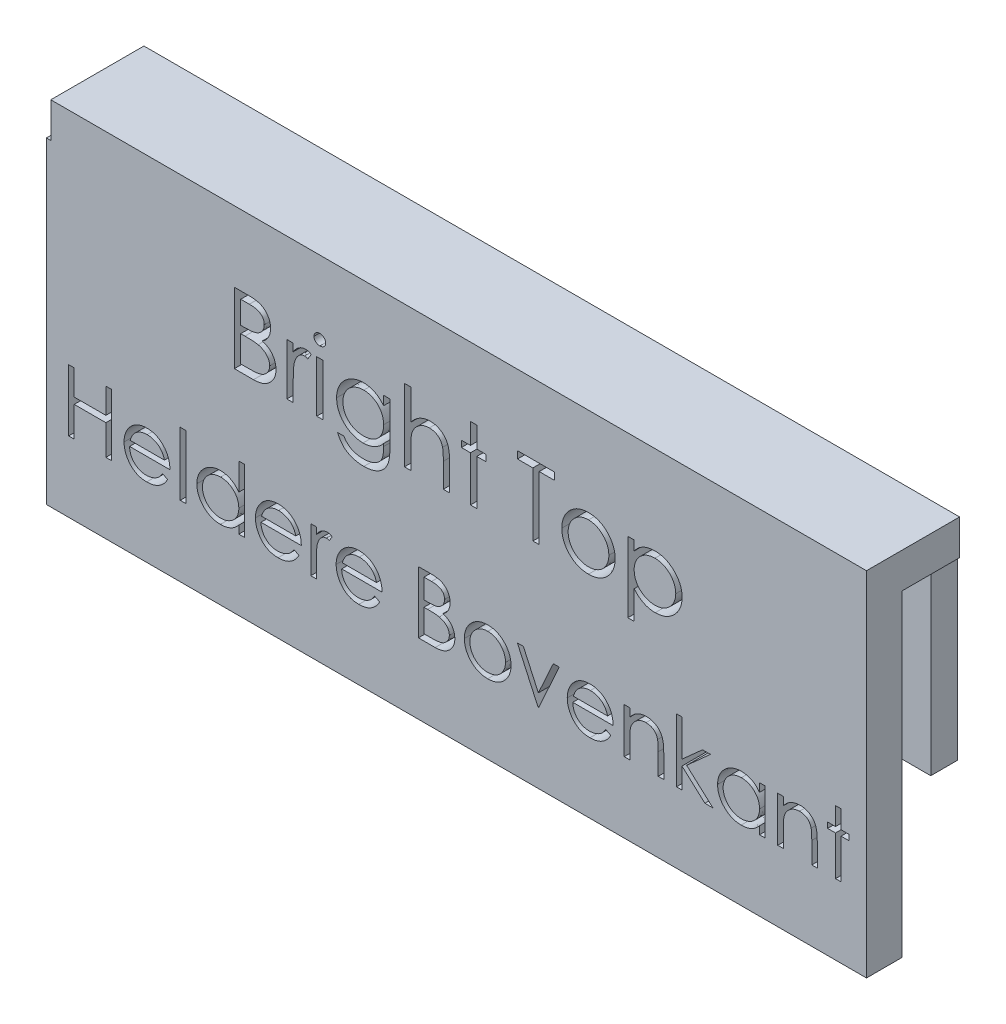
SolidWorks part; units mm, degrees
ref_plane "Front Plane" through (0, 0, 0) normal (0, 0, 1) x (1, 0, 0)
ref_plane "Top Plane" through (0, 0, 0) normal (0, 1, 0) x (1, 0, 0)
ref_plane "Right Plane" through (0, 0, 0) normal (1, 0, 0) x (0, 0, -1)
sketch "Sketch1" plane through (0, 0, 0) normal (0, 0, 1) x (1, 0, 0)
  line L0 (61.5, 25) -> (3, 25) construction
  line L1 (9, 25) -> (55.5, 25)
  line L2 (9, 25) -> (9, 7)
  line L3 (9, 7) -> (55.5, 7)
  line L4 (55.5, 25) -> (55.5, 7)
  line L5 (55.5, 15) -> (55.5, 25) construction
  line L6 (9, 15) -> (9, 25) construction
  line L7 (2, 2) -> (62.5, 2) construction
  dimension "D1" = 5
extrude "Boss-Extrude1" add sketch "Sketch1" along normal blind 2
sketch "Sketch3" plane through (0, 15, 0) normal (0, 1, 0) x (1, 0, 0)
  line L0 (9.2511, 3.2803) -> (9.2511, 1.7537)
  line L5 (9.2511, 1.7537) -> (55.39, 1.7537)
  line L6 (55.39, 3.2803) -> (55.39, 1.7537)
  line L7 (9.2511, 3.2803) -> (55.39, 3.2803)
extrude "Boss-Extrude2" add sketch "Sketch3" along normal up to surface (10 mm away) separate body
sketch "Sketch4" plane through (0, 25, 0) normal (0, 1, 0) x (1, 0, 0)
  line L1 (9.2511, 3.2803) -> (55.5, 3.2803)
  line L2 (9.2511, 3.2803) -> (9.2511, -2)
  line L3 (9.2511, -2) -> (55.5, -2)
  line L4 (55.5, 3.2803) -> (55.5, -2)
extrude "Boss-Extrude3" add sketch "Sketch4" along normal blind 2
sketch "Sketch5" plane through (0, 0, 2) normal (0, 0, 1) x (1, 0, 0)
  line L0 (9, 19) -> (55.5, 19) construction
  line L1 (9, 25) -> (9, 7) construction
  line L2 (55.5, 7) -> (55.5, 27) construction
  line L3 (9.2511, 27) -> (55.5, 27) construction
  line L4 (9, 11) -> (55.5, 11) construction
  line L5 (19.6603, 23) -> (20.4407, 23)
  line L6 (20.742, 19) -> (19.6603, 19)
  line L7 (19.6603, 19) -> (19.6603, 23)
  line L8 (20.0192, 22.5897) -> (20.0192, 21.3077)
  line L9 (20.0192, 21.3077) -> (20.2604, 21.3077)
  line L10 (20.5064, 22.5897) -> (20.0192, 22.5897)
  line L11 (20.0192, 20.8974) -> (20.0192, 19.4103)
  line L12 (20.0192, 19.4103) -> (20.5304, 19.4103)
  line L13 (20.2572, 20.8974) -> (20.0192, 20.8974)
  line L14 (22.6346, 21.9231) -> (22.9936, 21.9231)
  line L15 (22.9936, 21.9231) -> (22.9936, 21.4928)
  line L16 (24.0192, 21.8742) -> (23.8221, 21.5633)
  line L17 (22.9936, 19.9824) -> (22.9936, 19)
  line L18 (22.9936, 19) -> (22.6346, 19)
  line L19 (22.6346, 19) -> (22.6346, 21.9231)
  line L20 (24.3269, 21.9231) -> (24.6859, 21.9231)
  line L21 (24.6859, 21.9231) -> (24.6859, 19)
  line L22 (24.6859, 19) -> (24.3269, 19)
  line L23 (24.3269, 19) -> (24.3269, 21.9231)
  line L24 (28.1218, 21.9231) -> (28.4808, 21.9231)
  line L25 (28.4808, 21.9231) -> (28.4808, 19.6034)
  line L26 (25.5064, 18.7949) -> (25.8654, 18.7949)
  line L27 (28.1218, 19.4087) -> (28.1218, 19.5601)
  line L28 (28.1218, 21.4119) -> (28.1218, 21.9231)
  line L29 (29.3013, 23.1026) -> (29.6603, 23.1026)
  line L30 (29.6603, 23.1026) -> (29.6603, 21.371)
  line L31 (31.8654, 20.4928) -> (31.8654, 19)
  line L32 (31.8654, 19) -> (31.5064, 19)
  line L33 (31.5064, 19) -> (31.5064, 20.375)
  line L34 (29.6603, 20.0569) -> (29.6603, 19)
  line L35 (29.6603, 19) -> (29.3013, 19)
  line L36 (29.3013, 19) -> (29.3013, 23.1026)
  line L37 (33.0449, 23.1026) -> (33.4038, 23.1026)
  line L38 (33.4038, 23.1026) -> (33.4038, 21.9231)
  line L39 (33.4038, 21.9231) -> (33.9167, 21.9231)
  line L40 (33.9167, 21.9231) -> (33.9167, 21.5641)
  line L41 (33.9167, 21.5641) -> (33.4038, 21.5641)
  line L42 (33.4038, 21.5641) -> (33.4038, 19)
  line L43 (33.4038, 19) -> (33.0449, 19)
  line L44 (33.0449, 19) -> (33.0449, 21.5641)
  line L45 (33.0449, 21.5641) -> (32.5321, 21.5641)
  line L46 (32.5321, 21.5641) -> (32.5321, 21.9231)
  line L47 (32.5321, 21.9231) -> (33.0449, 21.9231)
  line L48 (33.0449, 21.9231) -> (33.0449, 23.1026)
  line L49 (35.7115, 22.5897) -> (35.7115, 23)
  line L50 (35.7115, 23) -> (37.8141, 23)
  line L51 (37.8141, 23) -> (37.8141, 22.5897)
  line L52 (37.8141, 22.5897) -> (36.9423, 22.5897)
  line L53 (36.9423, 22.5897) -> (36.9423, 19)
  line L54 (36.9423, 19) -> (36.5833, 19)
  line L55 (36.5833, 19) -> (36.5833, 22.5897)
  line L56 (36.5833, 22.5897) -> (35.7115, 22.5897)
  line L57 (41.9679, 21.9231) -> (42.3269, 21.9231)
  line L58 (42.3269, 21.9231) -> (42.3269, 21.3822)
  line L59 (42.3269, 19.5296) -> (42.3269, 17.9231)
  line L60 (42.3269, 17.9231) -> (41.9679, 17.9231)
  line L61 (41.9679, 17.9231) -> (41.9679, 21.9231)
  line L62 (10.2628, 14.5) -> (10.5769, 14.5)
  line L63 (10.5769, 14.5) -> (10.5769, 13.0641)
  line L64 (10.5769, 13.0641) -> (12.3718, 13.0641)
  line L65 (12.3718, 13.0641) -> (12.3718, 14.5)
  line L66 (12.3718, 14.5) -> (12.6859, 14.5)
  line L67 (12.6859, 14.5) -> (12.6859, 11)
  line L68 (12.6859, 11) -> (12.3718, 11)
  line L69 (12.3718, 11) -> (12.3718, 12.7051)
  line L70 (12.3718, 12.7051) -> (10.5769, 12.7051)
  line L71 (10.5769, 12.7051) -> (10.5769, 11)
  line L72 (10.5769, 11) -> (10.2628, 11)
  line L73 (10.2628, 11) -> (10.2628, 14.5)
  line L74 (15.5927, 11.8077) -> (15.8718, 11.6612)
  line L75 (16.0064, 12.2115) -> (13.7179, 12.2115)
  line L76 (13.7509, 12.5256) -> (15.6923, 12.5256)
  line L77 (16.5897, 14.5897) -> (16.9038, 14.5897)
  line L78 (16.9038, 14.5897) -> (16.9038, 11)
  line L79 (16.9038, 11) -> (16.5897, 11)
  line L80 (16.5897, 11) -> (16.5897, 14.5897)
  line L81 (20.2244, 14.5897) -> (20.2244, 11)
  line L82 (20.2244, 11) -> (19.9103, 11)
  line L83 (19.9103, 11) -> (19.9103, 11.4424)
  line L84 (19.9103, 13.0627) -> (19.9103, 14.5897)
  line L85 (19.9103, 14.5897) -> (20.2244, 14.5897)
  line L86 (23.0415, 11.8077) -> (23.3205, 11.6612)
  line L87 (23.4551, 12.2115) -> (21.1667, 12.2115)
  line L88 (21.1996, 12.5256) -> (23.141, 12.5256)
  line L89 (23.9936, 13.5577) -> (24.3077, 13.5577)
  line L90 (24.3077, 13.5577) -> (24.3077, 13.1812)
  line L91 (25.2051, 13.5149) -> (25.0327, 13.2429)
  line L92 (24.3077, 11.8596) -> (24.3077, 11)
  line L93 (24.3077, 11) -> (23.9936, 11)
  line L94 (23.9936, 11) -> (23.9936, 13.5577)
  line L95 (27.6184, 11.8077) -> (27.8974, 11.6612)
  line L96 (28.0321, 12.2115) -> (25.7436, 12.2115)
  line L97 (25.7765, 12.5256) -> (27.7179, 12.5256)
  line L98 (30.0962, 14.5) -> (30.779, 14.5)
  line L99 (31.0427, 11) -> (30.0962, 11)
  line L100 (30.0962, 11) -> (30.0962, 14.5)
  line L101 (30.4103, 14.141) -> (30.4103, 13.0192)
  line L102 (30.4103, 13.0192) -> (30.6213, 13.0192)
  line L103 (30.8365, 14.141) -> (30.4103, 14.141)
  line L104 (30.4103, 12.6603) -> (30.4103, 11.359)
  line L105 (30.4103, 11.359) -> (30.8576, 11.359)
  line L106 (30.6185, 12.6603) -> (30.4103, 12.6603)
  line L107 (35.7051, 13.5577) -> (36.0452, 13.5577)
  line L108 (36.0452, 13.5577) -> (36.8942, 11.6955)
  line L109 (36.8942, 11.6955) -> (37.7433, 13.5577)
  line L110 (37.7433, 13.5577) -> (38.0833, 13.5577)
  line L111 (38.0833, 13.5577) -> (36.9167, 11)
  line L112 (36.9167, 11) -> (36.8718, 11)
  line L113 (36.8718, 11) -> (35.7051, 13.5577)
  line L114 (40.721, 11.8077) -> (41, 11.6612)
  line L115 (41.1346, 12.2115) -> (38.8462, 12.2115)
  line L116 (38.8791, 12.5256) -> (40.8205, 12.5256)
  line L117 (41.7628, 13.5577) -> (42.0769, 13.5577)
  line L118 (42.0769, 13.5577) -> (42.0769, 13.0964)
  line L119 (44.0064, 12.3062) -> (44.0064, 11)
  line L120 (44.0064, 11) -> (43.6923, 11)
  line L121 (43.6923, 11) -> (43.6923, 12.2031)
  line L122 (42.0769, 11.9248) -> (42.0769, 11)
  line L123 (42.0769, 11) -> (41.7628, 11)
  line L124 (41.7628, 11) -> (41.7628, 13.5577)
  line L125 (44.7244, 14.5897) -> (45.0385, 14.5897)
  line L126 (45.0385, 14.5897) -> (45.0385, 12.5144)
  line L127 (45.0385, 12.5144) -> (46.2023, 13.5577)
  line L128 (46.2023, 13.5577) -> (46.6538, 13.5577)
  line L129 (46.6538, 13.5577) -> (45.3035, 12.3462)
  line L130 (45.3035, 12.3462) -> (46.7885, 11)
  line L131 (46.7885, 11) -> (46.3376, 11)
  line L132 (46.3376, 11) -> (45.0385, 12.1786)
  line L133 (45.0385, 12.1786) -> (45.0385, 11)
  line L134 (45.0385, 11) -> (44.7244, 11)
  line L135 (44.7244, 11) -> (44.7244, 14.5897)
  line L136 (49.75, 13.5577) -> (49.75, 11)
  line L137 (49.75, 11) -> (49.4359, 11)
  line L138 (49.4359, 11) -> (49.4359, 11.4424)
  line L139 (49.4359, 13.0844) -> (49.4359, 13.5577)
  line L140 (49.4359, 13.5577) -> (49.75, 13.5577)
  line L141 (50.4679, 13.5577) -> (50.7821, 13.5577)
  line L142 (50.7821, 13.5577) -> (50.7821, 13.0964)
  line L143 (52.7115, 12.3062) -> (52.7115, 11)
  line L144 (52.7115, 11) -> (52.3974, 11)
  line L145 (52.3974, 11) -> (52.3974, 12.2031)
  line L146 (50.7821, 11.9248) -> (50.7821, 11)
  line L147 (50.7821, 11) -> (50.4679, 11)
  line L148 (50.4679, 11) -> (50.4679, 13.5577)
  line L149 (53.7436, 14.5897) -> (54.0577, 14.5897)
  line L150 (54.0577, 14.5897) -> (54.0577, 13.5577)
  line L151 (54.0577, 13.5577) -> (54.5064, 13.5577)
  line L152 (54.5064, 13.5577) -> (54.5064, 13.2436)
  line L153 (54.5064, 13.2436) -> (54.0577, 13.2436)
  line L154 (54.0577, 13.2436) -> (54.0577, 11)
  line L155 (54.0577, 11) -> (53.7436, 11)
  line L156 (53.7436, 11) -> (53.7436, 13.2436)
  line L157 (53.7436, 13.2436) -> (53.2949, 13.2436)
  line L158 (53.2949, 13.2436) -> (53.2949, 13.5577)
  line L159 (53.2949, 13.5577) -> (53.7436, 13.5577)
  line L160 (53.7436, 13.5577) -> (53.7436, 14.5897)
  spline S0 degree 3 poles (20.4407, 23) (20.5148, 23.0006) (20.6226, 22.9966) (20.7615, 22.9851) (20.8556, 22.9721) (20.9428, 22.9563) (21.0234, 22.9372) (21.0972, 22.9143) (21.1854, 22.8779) (21.2859, 22.8239) (21.3947, 22.7439) (21.4877, 22.6462) (21.5679, 22.5359) (21.6316, 22.4146) (21.694, 22.2407) (21.7124, 22.1021) (21.7115, 22.0088) knots 0 0 0 0 0.121323 0.17668 0.228365 0.276868 0.321879 0.364099 0.403356 0.477968 0.550535 0.623584 0.698175 0.773354 0.847281 1 1 1 1
  spline S1 degree 3 poles (21.7115, 22.0088) (21.7122, 21.922) (21.6975, 21.7932) (21.6476, 21.63) (21.5965, 21.5157) (21.5301, 21.4105) (21.4241, 21.2797) (21.321, 21.2033) (21.2492, 21.1579) knots 0 0 0 0 0.256581 0.380552 0.503623 0.625739 0.747549 1 1 1 1
  spline S2 degree 3 poles (21.2492, 21.1579) (21.3364, 21.1257) (21.4599, 21.0739) (21.6043, 20.9838) (21.6916, 20.9137) (21.7663, 20.8382) (21.8315, 20.7561) (21.8871, 20.6663) (21.9348, 20.5698) (21.972, 20.4677) (22.0096, 20.3237) (22.0185, 20.211) (22.0192, 20.1354) knots 0 0 0 0 0.202914 0.2903 0.370223 0.446384 0.521397 0.598291 0.676142 0.755529 0.834887 1 1 1 1
  spline S3 degree 3 poles (22.0192, 20.1354) (22.0187, 20.0587) (22.0095, 19.9446) (21.9722, 19.7988) (21.9345, 19.6953) (21.8851, 19.5962) (21.8251, 19.5016) (21.7535, 19.4123) (21.6735, 19.3274) (21.5829, 19.251) (21.4851, 19.183) (21.379, 19.127) (21.2663, 19.08) (21.1456, 19.0442) (20.9709, 19.0097) (20.8348, 18.9989) (20.742, 19) knots 0 0 0 0 0.120335 0.17818 0.235235 0.292683 0.351186 0.410457 0.47172 0.533761 0.595739 0.657888 0.721295 0.786823 0.854686 1 1 1 1
  spline S4 degree 3 poles (20.2604, 21.3077) (20.3285, 21.309) (20.4273, 21.3089) (20.554, 21.3186) (20.6383, 21.3257) (20.7153, 21.3372) (20.7847, 21.3509) (20.8477, 21.3654) (20.9203, 21.3901) (21.0027, 21.4265) (21.0905, 21.4831) (21.1679, 21.5504) (21.2333, 21.6281) (21.2867, 21.7137) (21.3368, 21.8368) (21.3541, 21.9354) (21.3526, 22.0016) knots 0 0 0 0 0.1397 0.202289 0.2606 0.31319 0.361739 0.405706 0.44554 0.518832 0.589778 0.658867 0.72843 0.797283 0.864815 1 1 1 1
  spline S5 degree 3 poles (21.3526, 22.0016) (21.3524, 22.0451) (21.3471, 22.1094) (21.3247, 22.1905) (21.3036, 22.2473) (21.2741, 22.2993) (21.2394, 22.3484) (21.1975, 22.3929) (21.1498, 22.4344) (21.0949, 22.4713) (21.0329, 22.5035) (20.963, 22.5295) (20.8863, 22.5523) (20.8017, 22.5683) (20.6748, 22.5867) (20.5751, 22.5892) (20.5064, 22.5897) knots 0 0 0 0 0.111818 0.164402 0.21587 0.266841 0.317479 0.369902 0.4234 0.479718 0.539241 0.602431 0.67103 0.744485 0.823454 1 1 1 1
  spline S6 degree 3 poles (20.5304, 19.4103) (20.601, 19.4113) (20.7029, 19.4119) (20.8338, 19.4206) (20.9203, 19.4305) (20.9998, 19.4412) (21.0715, 19.4556) (21.1358, 19.4721) (21.2104, 19.4976) (21.2944, 19.5373) (21.385, 19.5971) (21.4654, 19.6683) (21.5338, 19.7507) (21.5898, 19.8404) (21.6442, 19.9665) (21.6604, 20.0681) (21.6603, 20.1354) knots 0 0 0 0 0.139739 0.201795 0.259822 0.312206 0.360773 0.40454 0.443698 0.516841 0.587874 0.657965 0.728969 0.799308 0.866636 1 1 1 1
  spline S7 degree 3 poles (21.6603, 20.1354) (21.6611, 20.1774) (21.6547, 20.2395) (21.6361, 20.3198) (21.6184, 20.3777) (21.5925, 20.4328) (21.5624, 20.4862) (21.527, 20.5379) (21.4718, 20.6033) (21.3916, 20.6786) (21.2354, 20.78) (21.1002, 20.8282) (21.0056, 20.8502) knots 0 0 0 0 0.119602 0.177503 0.235143 0.292133 0.350871 0.410098 0.470732 0.594829 0.722579 1 1 1 1
  spline S8 degree 3 poles (21.0056, 20.8502) (20.9636, 20.8595) (20.8949, 20.8698) (20.7966, 20.8797) (20.7081, 20.8857) (20.6096, 20.8919) (20.4581, 20.8953) (20.3395, 20.8979) (20.2572, 20.8974) knots 0 0 0 0 0.171953 0.277057 0.394731 0.526177 0.671345 1 1 1 1
  spline S9 degree 3 poles (22.9936, 21.4928) (23.0428, 21.5702) (23.1204, 21.6773) (23.2413, 21.7947) (23.3301, 21.8616) (23.4219, 21.9116) (23.5449, 21.9604) (23.6426, 21.9739) (23.7067, 21.9744) knots 0 0 0 0 0.306112 0.438367 0.560541 0.675317 0.786114 1 1 1 1
  spline S10 degree 3 poles (23.7067, 21.9744) (23.7581, 21.974) (23.8684, 21.9547) (23.9686, 21.9049) (24.0192, 21.8742) knots 0 0 0 0 0.463523 1 1 1 1
  spline S11 degree 3 poles (23.8221, 21.5633) (23.7894, 21.5778) (23.7306, 21.6044) (23.6668, 21.615) (23.6386, 21.6154) knots 0 0 0 0 0.56023 1 1 1 1
  spline S12 degree 3 poles (23.6386, 21.6154) (23.5797, 21.6155) (23.4896, 21.5939) (23.3811, 21.5289) (23.3146, 21.4739) (23.2631, 21.4207) (23.2264, 21.3742) (23.1927, 21.3221) (23.1605, 21.2653) (23.1312, 21.2027) (23.0936, 21.1101) (23.0713, 21.0364) (23.0577, 20.9856) knots 0 0 0 0 0.191338 0.295191 0.410312 0.47193 0.536425 0.603119 0.674118 0.749332 0.828283 1 1 1 1
  spline S13 degree 3 poles (23.0577, 20.9856) (23.0443, 20.9345) (23.0312, 20.8486) (23.0172, 20.7232) (23.009, 20.6056) (23.0015, 20.4723) (22.9955, 20.2629) (22.993, 20.0978) (22.9936, 19.9824) knots 0 0 0 0 0.156938 0.2586 0.375891 0.508166 0.656238 1 1 1 1
  spline S14 degree 3 poles (24.5048, 23.1538) (24.5482, 23.1538) (24.6138, 23.1438) (24.6912, 23.1041) (24.7422, 23.0647) (24.7858, 23.0183) (24.827, 22.9462) (24.84, 22.8853) (24.8397, 22.8446) knots 0 0 0 0 0.258284 0.384341 0.51198 0.638632 0.75923 1 1 1 1
  spline S15 degree 3 poles (24.8397, 22.8446) (24.8398, 22.8046) (24.8269, 22.7447) (24.7856, 22.6739) (24.7422, 22.6276) (24.6912, 22.5883) (24.6138, 22.5485) (24.5482, 22.5385) (24.5048, 22.5385) knots 0 0 0 0 0.237546 0.357497 0.484917 0.613329 0.74015 1 1 1 1
  spline S16 degree 3 poles (24.5048, 22.5385) (24.4621, 22.5382) (24.3975, 22.549) (24.3208, 22.5883) (24.2698, 22.6273) (24.2273, 22.6741) (24.1858, 22.7446) (24.173, 22.8047) (24.1731, 22.8446) knots 0 0 0 0 0.256661 0.384213 0.513365 0.640443 0.761085 1 1 1 1
  spline S17 degree 3 poles (24.1731, 22.8446) (24.1729, 22.8853) (24.1857, 22.9463) (24.227, 23.0181) (24.2698, 23.065) (24.3208, 23.104) (24.3975, 23.1434) (24.4621, 23.1541) (24.5048, 23.1538) knots 0 0 0 0 0.242149 0.363437 0.489745 0.618115 0.744894 1 1 1 1
  spline S18 degree 3 poles (28.4808, 19.6034) (28.4803, 19.508) (28.479, 19.3699) (28.4662, 19.1933) (28.4556, 19.0758) (28.4405, 18.9689) (28.4171, 18.8458) (28.3939, 18.7597) (28.3742, 18.7067) knots 0 0 0 0 0.315489 0.456291 0.585864 0.705429 0.813371 1 1 1 1
  spline S19 degree 3 poles (28.3742, 18.7067) (28.3506, 18.6415) (28.3076, 18.5475) (28.2362, 18.4312) (28.1759, 18.3507) (28.1083, 18.2764) (28.035, 18.2068) (27.9547, 18.1433) (27.8674, 18.0869) (27.775, 18.0362) (27.6777, 17.9923) (27.576, 17.954) (27.4689, 17.9253) (27.3581, 17.9005) (27.2013, 17.8785) (27.0809, 17.8712) (26.9992, 17.8718) knots 0 0 0 0 0.120906 0.179424 0.237607 0.295938 0.354218 0.413537 0.474087 0.535121 0.596988 0.66002 0.724277 0.790012 0.857748 1 1 1 1
  spline S20 degree 3 poles (26.9992, 17.8718) (26.8811, 17.8702) (26.708, 17.8852) (26.4851, 17.9285) (26.3325, 17.9761) (26.1916, 18.0344) (26.0634, 18.1014) (25.9492, 18.1782) (25.8462, 18.2656) (25.7532, 18.3696) (25.6303, 18.5415) (25.554, 18.6893) (25.5064, 18.7949) knots 0 0 0 0 0.188474 0.27684 0.362137 0.443437 0.520166 0.59271 0.662917 0.735419 0.814881 1 1 1 1
  spline S21 degree 3 poles (25.8654, 18.7949) (25.9181, 18.7031) (26.0148, 18.5785) (26.172, 18.4443) (26.3016, 18.3644) (26.4459, 18.3042) (26.6661, 18.2444) (26.8433, 18.2313) (26.9647, 18.2308) knots 0 0 0 0 0.243805 0.360062 0.475112 0.593525 0.71935 1 1 1 1
  spline S22 degree 3 poles (26.9647, 18.2308) (27.0852, 18.2314) (27.261, 18.2446) (27.4799, 18.3042) (27.6223, 18.3643) (27.7469, 18.4379) (27.8544, 18.5202) (27.9414, 18.613) (27.9999, 18.6985) (28.0363, 18.7746) (28.0595, 18.8401) (28.0783, 18.9143) (28.094, 18.9967) (28.107, 19.0876) (28.1185, 19.2257) (28.1224, 19.3338) (28.1218, 19.4087) knots 0 0 0 0 0.189264 0.274463 0.355023 0.43092 0.501086 0.566608 0.629721 0.662711 0.698766 0.738611 0.782581 0.830409 0.882578 1 1 1 1
  spline S23 degree 3 poles (28.1218, 19.5601) (28.0522, 19.4722) (27.9348, 19.3509) (27.7521, 19.2212) (27.6046, 19.1415) (27.4494, 19.078) (27.2335, 19.018) (27.0658, 18.9992) (26.9535, 19) knots 0 0 0 0 0.250895 0.374719 0.499826 0.624964 0.749039 1 1 1 1
  spline S24 degree 3 poles (26.9535, 19) (26.8871, 18.9997) (26.788, 19.0068) (26.6578, 19.0269) (26.5622, 19.0487) (26.4682, 19.0767) (26.3759, 19.1116) (26.2845, 19.1512) (26.1958, 19.1978) (26.1106, 19.2496) (26.0295, 19.3058) (25.9529, 19.366) (25.8817, 19.4308) (25.8158, 19.5001) (25.7545, 19.5732) (25.6986, 19.6511) (25.6472, 19.7324) (25.6025, 19.8176) (25.5634, 19.9049) (25.5293, 19.9941) (25.5021, 20.0854) (25.4814, 20.1789) (25.4606, 20.3072) (25.4557, 20.4053) (25.4551, 20.4712) knots 0 0 0 0 0.085222 0.127202 0.169025 0.210882 0.252963 0.295628 0.338553 0.381463 0.423582 0.465066 0.506312 0.54704 0.587676 0.628675 0.669946 0.711036 0.751996 0.792673 0.833446 0.874191 0.915494 1 1 1 1
  spline S25 degree 3 poles (25.4551, 20.4712) (25.4548, 20.5374) (25.4621, 20.6358) (25.4818, 20.7654) (25.5048, 20.86) (25.5326, 20.9533) (25.567, 21.0446) (25.6084, 21.1341) (25.6553, 21.2217) (25.708, 21.3063) (25.7657, 21.3867) (25.8286, 21.4622) (25.8958, 21.5337) (25.9681, 21.6004) (26.0455, 21.6621) (26.1272, 21.7199) (26.2134, 21.7726) (26.3028, 21.8193) (26.3933, 21.8618) (26.4858, 21.8955) (26.5788, 21.9253) (26.6739, 21.9463) (26.802, 21.9681) (26.8997, 21.9743) (26.9647, 21.9744) knots 0 0 0 0 0.083905 0.125069 0.166158 0.20721 0.248491 0.289878 0.33217 0.374476 0.416225 0.45761 0.499073 0.540553 0.582249 0.62455 0.667433 0.710323 0.752467 0.794065 0.835216 0.876228 0.917446 1 1 1 1
  spline S26 degree 3 poles (26.9647, 21.9744) (27.0709, 21.9742) (27.2288, 21.9592) (27.4318, 21.9074) (27.5779, 21.8526) (27.7206, 21.7776) (27.9132, 21.6409) (28.04, 21.5075) (28.1218, 21.4119) knots 0 0 0 0 0.238762 0.354755 0.470359 0.589144 0.716329 1 1 1 1
  spline S27 degree 3 poles (26.9936, 21.6154) (26.8896, 21.6158) (26.7349, 21.5963) (26.5378, 21.5326) (26.3988, 21.4651) (26.2686, 21.3827) (26.1531, 21.2829) (26.0521, 21.1689) (25.9666, 21.0417) (25.8986, 20.9046) (25.8338, 20.7111) (25.8133, 20.5589) (25.8141, 20.4567) knots 0 0 0 0 0.169309 0.252218 0.336756 0.420595 0.502741 0.584804 0.668268 0.751823 0.833629 1 1 1 1
  spline S28 degree 3 poles (25.8141, 20.4567) (25.8138, 20.3805) (25.8231, 20.2675) (25.8576, 20.1231) (25.8935, 20.0219) (25.938, 19.9253) (25.994, 19.8341) (26.0599, 19.7483) (26.1352, 19.6684) (26.2181, 19.5957) (26.3081, 19.5317) (26.405, 19.4795) (26.5063, 19.4343) (26.6147, 19.4013) (26.7692, 19.3669) (26.8903, 19.3594) (26.972, 19.359) knots 0 0 0 0 0.127803 0.189056 0.248395 0.307691 0.366977 0.42734 0.488795 0.550674 0.612045 0.673369 0.73493 0.79781 0.862892 1 1 1 1
  spline S29 degree 3 poles (26.972, 19.359) (27.0545, 19.359) (27.1761, 19.3676) (27.3318, 19.4001) (27.4397, 19.4339) (27.5415, 19.477) (27.6362, 19.5316) (27.7258, 19.5937) (27.8073, 19.6662) (27.8811, 19.746) (27.9453, 19.8329) (28.0001, 19.9256) (28.0454, 20.0239) (28.08, 20.1288) (28.1119, 20.2799) (28.1227, 20.3975) (28.1218, 20.4776) knots 0 0 0 0 0.137122 0.201487 0.263765 0.32456 0.384739 0.444905 0.505232 0.565494 0.6251 0.68435 0.743883 0.804608 0.867239 1 1 1 1
  spline S30 degree 3 poles (28.1218, 20.4776) (28.1223, 20.5815) (28.1056, 20.7357) (28.0435, 20.9292) (27.9797, 21.0623) (27.8997, 21.1844) (27.8034, 21.2933) (27.6924, 21.3892) (27.567, 21.4691) (27.4321, 21.5336) (27.2432, 21.5986) (27.0931, 21.6141) (26.9936, 21.6154) knots 0 0 0 0 0.174349 0.257613 0.339527 0.420997 0.501579 0.582542 0.666133 0.750049 0.832743 1 1 1 1
  spline S31 degree 3 poles (29.6603, 21.371) (29.7324, 21.467) (29.8521, 21.5964) (30.0298, 21.7413) (30.1673, 21.8258) (30.3103, 21.8924) (30.51, 21.9562) (30.6673, 21.9741) (30.7724, 21.9744) knots 0 0 0 0 0.273996 0.400684 0.522555 0.641534 0.759969 1 1 1 1
  spline S32 degree 3 poles (30.7724, 21.9744) (30.878, 21.9737) (31.0356, 21.9565) (31.2305, 21.8848) (31.3638, 21.8127) (31.4836, 21.7227) (31.5898, 21.6189) (31.6764, 21.4986) (31.7354, 21.3875) (31.7738, 21.2886) (31.7981, 21.2037) (31.8186, 21.1092) (31.8366, 21.005) (31.8485, 20.8907) (31.8619, 20.719) (31.8663, 20.5853) (31.8654, 20.4928) knots 0 0 0 0 0.151155 0.223454 0.295497 0.36692 0.436794 0.506696 0.577864 0.615912 0.658048 0.703776 0.75408 0.808979 0.867913 1 1 1 1
  spline S33 degree 3 poles (31.5064, 20.375) (31.5059, 20.4511) (31.5056, 20.5601) (31.5013, 20.6988) (31.4964, 20.7872) (31.4911, 20.8652) (31.4824, 20.9486) (31.4729, 21.0057) (31.4647, 21.0401) knots 0 0 0 0 0.342141 0.489871 0.623312 0.740056 0.841468 1 1 1 1
  spline S34 degree 3 poles (31.4647, 21.0401) (31.4426, 21.1277) (31.3962, 21.2527) (31.2953, 21.3921) (31.2064, 21.4743) (31.1029, 21.5387) (30.9384, 21.6009) (30.8024, 21.6158) (30.7091, 21.6154) knots 0 0 0 0 0.261954 0.379638 0.494379 0.609866 0.729887 1 1 1 1
  spline S35 degree 3 poles (30.7091, 21.6154) (30.652, 21.6157) (30.5666, 21.6091) (30.4562, 21.5853) (30.3757, 21.5614) (30.2987, 21.5289) (30.2229, 21.4913) (30.1504, 21.4452) (30.0801, 21.3935) (30.0146, 21.3363) (29.9536, 21.2759) (29.8993, 21.2116) (29.85, 21.1444) (29.8076, 21.0734) (29.7578, 20.9742) (29.7299, 20.8954) (29.7155, 20.8413) knots 0 0 0 0 0.126694 0.189084 0.250363 0.312516 0.374243 0.43785 0.502657 0.567745 0.630576 0.692772 0.754268 0.815121 0.876051 1 1 1 1
  spline S36 degree 3 poles (29.7155, 20.8413) (29.7049, 20.7991) (29.6928, 20.7294) (29.6811, 20.6283) (29.673, 20.5359) (29.6681, 20.4319) (29.6606, 20.2712) (29.6608, 20.1448) (29.6603, 20.0569) knots 0 0 0 0 0.165611 0.269045 0.387448 0.518827 0.665394 1 1 1 1
  spline S37 degree 3 poles (39.7388, 21.9744) (39.8463, 21.9755) (40.0054, 21.96) (40.209, 21.9089) (40.3528, 21.8573) (40.4881, 21.7879) (40.6622, 21.6764) (40.7783, 21.5704) (40.8494, 21.4928) knots 0 0 0 0 0.258332 0.382134 0.503804 0.624693 0.746871 1 1 1 1
  spline S38 degree 3 poles (40.8494, 21.4928) (40.9145, 21.4215) (41.0018, 21.3073) (41.0958, 21.1423) (41.152, 21.0141) (41.1961, 20.8811) (41.2386, 20.6949) (41.2495, 20.5506) (41.25, 20.4535) knots 0 0 0 0 0.253834 0.376506 0.498534 0.621368 0.744565 1 1 1 1
  spline S39 degree 3 poles (41.25, 20.4535) (41.2506, 20.3557) (41.2372, 20.2105) (41.193, 20.0226) (41.1464, 19.8879) (41.0866, 19.7577) (41.0136, 19.6327) (40.9269, 19.5125) (40.8286, 19.3982) (40.7199, 19.2929) (40.6021, 19.2011) (40.4773, 19.1224) (40.344, 19.0591) (40.2034, 19.0092) (40.0022, 18.9613) (39.845, 18.9491) (39.7388, 18.9487) knots 0 0 0 0 0.123337 0.183265 0.243172 0.302898 0.363774 0.425605 0.489659 0.553785 0.616222 0.677854 0.739517 0.802097 0.865866 1 1 1 1
  spline S40 degree 3 poles (39.7388, 18.9487) (39.632, 18.9492) (39.4743, 18.9612) (39.2726, 19.0091) (39.1317, 19.0592) (38.9979, 19.1224) (38.8724, 19.2009) (38.7544, 19.2929) (38.6458, 19.3982) (38.5475, 19.5125) (38.4608, 19.6327) (38.3878, 19.7577) (38.3279, 19.8879) (38.2813, 20.0226) (38.2372, 20.2105) (38.2238, 20.3557) (38.2244, 20.4535) knots 0 0 0 0 0.134635 0.198324 0.260825 0.322714 0.384555 0.446913 0.510958 0.574931 0.636685 0.697483 0.757134 0.816966 0.876818 1 1 1 1
  spline S41 degree 3 poles (38.2244, 20.4535) (38.2249, 20.5503) (38.2358, 20.6943) (38.2781, 20.8801) (38.3224, 21.0125) (38.379, 21.1402) (38.4717, 21.3057) (38.5605, 21.4189) (38.625, 21.4904) knots 0 0 0 0 0.255238 0.378679 0.501088 0.622714 0.746241 1 1 1 1
  spline S42 degree 3 poles (38.625, 21.4904) (38.6954, 21.5691) (38.8126, 21.674) (38.9863, 21.7878) (39.1231, 21.8558) (39.2667, 21.9093) (39.4711, 21.9599) (39.6307, 21.9753) (39.7388, 21.9744) knots 0 0 0 0 0.252713 0.374819 0.496436 0.617911 0.741288 1 1 1 1
  spline S43 degree 3 poles (39.7372, 21.6154) (39.6606, 21.6152) (39.5469, 21.6048) (39.4006, 21.5693) (39.2961, 21.5321) (39.196, 21.484) (39.1001, 21.4249) (39.0081, 21.3556) (38.922, 21.2762) (38.8429, 21.1895) (38.7738, 21.0971) (38.715, 21.0005) (38.6661, 20.8996) (38.6296, 20.7935) (38.5937, 20.6447) (38.5835, 20.529) (38.5833, 20.4511) knots 0 0 0 0 0.126044 0.187165 0.247399 0.30838 0.36978 0.432584 0.497641 0.562401 0.625557 0.687332 0.748313 0.809791 0.871768 1 1 1 1
  spline S44 degree 3 poles (38.5833, 20.4511) (38.5836, 20.3498) (38.6014, 20.1974) (38.6681, 20.0054) (38.735, 19.8687) (38.8189, 19.7423) (38.9177, 19.6295) (39.0305, 19.5321) (39.1557, 19.4513) (39.291, 19.3872) (39.4835, 19.3257) (39.6351, 19.3065) (39.7372, 19.3077) knots 0 0 0 0 0.168179 0.251488 0.335841 0.419834 0.502345 0.583649 0.665931 0.748717 0.831047 1 1 1 1
  spline S45 degree 3 poles (39.7372, 19.3077) (39.8392, 19.3067) (39.9907, 19.3254) (40.1828, 19.3874) (40.3179, 19.4513) (40.4431, 19.5324) (40.5566, 19.6289) (40.6546, 19.7426) (40.7385, 19.8689) (40.8064, 20.0052) (40.8728, 20.1975) (40.8908, 20.3497) (40.891, 20.4511) knots 0 0 0 0 0.168983 0.250908 0.333708 0.416005 0.49766 0.579893 0.663902 0.748466 0.831791 1 1 1 1
  spline S46 degree 3 poles (40.891, 20.4511) (40.8908, 20.529) (40.8806, 20.6447) (40.8447, 20.7935) (40.8082, 20.8996) (40.7595, 21.0007) (40.6996, 21.0968) (40.6307, 21.1898) (40.5507, 21.2759) (40.4647, 21.3556) (40.3727, 21.4249) (40.2769, 21.4837) (40.1771, 21.5325) (40.0726, 21.569) (39.9268, 21.6051) (39.8134, 21.615) (39.7372, 21.6154) knots 0 0 0 0 0.128274 0.19027 0.251768 0.312769 0.374793 0.43797 0.503047 0.568125 0.63095 0.692369 0.752973 0.813641 0.874355 1 1 1 1
  spline S47 degree 3 poles (42.3269, 21.3822) (42.398, 21.4797) (42.5173, 21.6122) (42.7016, 21.7541) (42.8469, 21.8357) (43.0005, 21.8972) (43.2191, 21.9591) (43.3918, 21.974) (43.508, 21.9744) knots 0 0 0 0 0.263045 0.386061 0.505771 0.625178 0.746148 1 1 1 1
  spline S48 degree 3 poles (43.508, 21.9744) (43.6105, 21.9733) (43.7628, 21.9619) (43.9587, 21.9154) (44.0976, 21.8658) (44.2316, 21.8045) (44.3588, 21.7271) (44.4809, 21.6375) (44.5951, 21.5343) (44.7006, 21.4228) (44.7919, 21.3027) (44.8706, 21.1782) (44.9342, 21.0473) (44.984, 20.9109) (45.032, 20.7192) (45.0443, 20.5699) (45.0449, 20.4696) knots 0 0 0 0 0.128636 0.190653 0.252125 0.313446 0.375227 0.438498 0.503285 0.56801 0.630879 0.692154 0.752552 0.813191 0.873985 1 1 1 1
  spline S49 degree 3 poles (45.0449, 20.4696) (45.0446, 20.3673) (45.0315, 20.2156) (44.985, 20.0205) (44.9359, 19.8819) (44.8722, 19.7493) (44.7949, 19.6229) (44.7036, 19.5027) (44.5992, 19.3903) (44.486, 19.2868) (44.365, 19.1962) (44.2381, 19.1202) (44.1059, 19.0566) (43.9673, 19.0088) (43.7727, 18.962) (43.6212, 18.9491) (43.5192, 18.9487) knots 0 0 0 0 0.128034 0.189574 0.25058 0.311733 0.37325 0.435763 0.500346 0.564949 0.627528 0.689157 0.749865 0.81076 0.8723 1 1 1 1
  spline S50 degree 3 poles (43.5192, 18.9487) (43.4044, 18.9474) (43.2347, 18.967) (43.0172, 19.0271) (42.8638, 19.0918) (42.7174, 19.1744) (42.5287, 19.311) (42.4041, 19.4381) (42.3269, 19.5296) knots 0 0 0 0 0.250548 0.37123 0.492116 0.613401 0.737997 1 1 1 1
  spline S51 degree 3 poles (43.5048, 21.6154) (43.4247, 21.6166) (43.3065, 21.6051) (43.1537, 21.5712) (43.0462, 21.5337) (42.943, 21.4875) (42.8451, 21.4298) (42.7525, 21.3616) (42.6653, 21.2843) (42.5866, 21.199) (42.517, 21.1081) (42.4584, 21.0115) (42.4099, 20.9102) (42.3729, 20.8034) (42.3373, 20.6524) (42.3271, 20.5346) (42.3269, 20.4551) knots 0 0 0 0 0.130024 0.192374 0.253884 0.314896 0.375806 0.438242 0.501591 0.564881 0.626533 0.687516 0.748106 0.808796 0.870822 1 1 1 1
  spline S52 degree 3 poles (42.3269, 20.4551) (42.3271, 20.3514) (42.3444, 20.197) (42.4084, 20.0029) (42.4753, 19.8687) (42.5598, 19.7452) (42.6616, 19.6347) (42.7798, 19.5378) (42.9125, 19.4562) (43.0547, 19.39) (43.2526, 19.3263) (43.4074, 19.3079) (43.5104, 19.3077) knots 0 0 0 0 0.169344 0.251061 0.332326 0.413189 0.494299 0.576654 0.661785 0.747765 0.831967 1 1 1 1
  spline S53 degree 3 poles (43.5104, 19.3077) (43.6115, 19.3071) (43.7626, 19.3275) (43.9556, 19.3903) (44.093, 19.4583) (44.2219, 19.5417) (44.3384, 19.6418) (44.4401, 19.7578) (44.5268, 19.8869) (44.5966, 20.0254) (44.6666, 20.2156) (44.6847, 20.3663) (44.6859, 20.4655) knots 0 0 0 0 0.165574 0.248159 0.332033 0.416257 0.499525 0.583039 0.668596 0.754035 0.83692 1 1 1 1
  spline S54 degree 3 poles (44.6859, 20.4655) (44.6873, 20.5656) (44.6649, 20.7152) (44.5992, 20.9065) (44.5278, 21.0431) (44.443, 21.172) (44.3404, 21.2858) (44.2254, 21.3854) (44.0966, 21.4677) (43.9584, 21.5331) (43.763, 21.5978) (43.6082, 21.6149) (43.5048, 21.6154) knots 0 0 0 0 0.163349 0.245826 0.330367 0.415198 0.497941 0.580476 0.66374 0.747513 0.830399 1 1 1 1
  spline S55 degree 3 poles (15.8718, 11.6612) (15.8303, 11.5835) (15.7608, 11.4745) (15.6539, 11.3447) (15.5688, 11.263) (15.4791, 11.1917) (15.3844, 11.1294) (15.2841, 11.0763) (15.1783, 11.0315) (15.066, 10.9971) (14.9036, 10.9638) (14.7767, 10.9551) (14.6904, 10.9551) knots 0 0 0 0 0.181661 0.265874 0.346355 0.4246 0.501903 0.579992 0.658443 0.738672 0.821894 1 1 1 1
  spline S56 degree 3 poles (14.6904, 10.9551) (14.5946, 10.9552) (14.4537, 10.9662) (14.2745, 11.0093) (14.1513, 11.0532) (14.0365, 11.1107) (13.93, 11.1806) (13.8312, 11.2628) (13.7432, 11.3578) (13.6639, 11.4595) (13.594, 11.5654) (13.5356, 11.6754) (13.488, 11.7887) (13.4496, 11.9045) (13.4135, 12.065) (13.4048, 12.1888) (13.4038, 12.2718) knots 0 0 0 0 0.139629 0.204797 0.268135 0.329814 0.391301 0.453434 0.516552 0.579631 0.641119 0.701294 0.76081 0.819932 0.87892 1 1 1 1
  spline S57 degree 3 poles (13.4038, 12.2718) (13.4048, 12.3496) (13.4121, 12.4658) (13.4437, 12.6163) (13.4759, 12.7252) (13.5174, 12.8307) (13.5856, 12.9682) (13.6508, 13.0643) (13.6983, 13.1258) knots 0 0 0 0 0.253768 0.377428 0.500551 0.623296 0.746578 1 1 1 1
  spline S58 degree 3 poles (13.6983, 13.1258) (13.7589, 13.2015) (13.8577, 13.3074) (14.0123, 13.4182) (14.1339, 13.4862) (14.2642, 13.5378) (14.4508, 13.5903) (14.5987, 13.6014) (14.6981, 13.6026) knots 0 0 0 0 0.253589 0.374643 0.49534 0.616325 0.739759 1 1 1 1
  spline S59 degree 3 poles (14.6981, 13.6026) (14.8009, 13.603) (14.9529, 13.5881) (15.1454, 13.5348) (15.2793, 13.4797) (15.405, 13.4085) (15.5632, 13.2895) (15.6667, 13.1798) (15.7281, 13.0992) knots 0 0 0 0 0.259033 0.38188 0.502258 0.622752 0.744743 1 1 1 1
  spline S60 degree 3 poles (15.7281, 13.0992) (15.774, 13.0403) (15.8339, 12.9446) (15.8975, 12.8078) (15.9358, 12.699) (15.9669, 12.5851) (15.9975, 12.4228) (16.0048, 12.2968) (16.0064, 12.2115) knots 0 0 0 0 0.236255 0.356174 0.47725 0.60154 0.729618 1 1 1 1
  spline S61 degree 3 poles (13.7179, 12.2115) (13.7197, 12.1453) (13.7286, 12.0474) (13.7589, 11.9222) (13.7901, 11.8351) (13.828, 11.7522) (13.8744, 11.674) (13.9297, 11.601) (13.9915, 11.5324) (14.0602, 11.4714) (14.1325, 11.4167) (14.2094, 11.3709) (14.2902, 11.3337) (14.375, 11.3047) (14.495, 11.2776) (14.5881, 11.2689) (14.6511, 11.2692) knots 0 0 0 0 0.134476 0.198391 0.260753 0.321829 0.383037 0.444653 0.507398 0.569825 0.630778 0.690929 0.750945 0.811049 0.872331 1 1 1 1
  spline S62 degree 3 poles (14.6511, 11.2692) (14.7133, 11.2689) (14.8066, 11.2763) (14.9285, 11.3018) (15.0177, 11.3276) (15.1033, 11.3592) (15.1826, 11.3973) (15.2554, 11.4395) (15.3236, 11.4877) (15.3896, 11.5467) (15.4831, 11.6515) (15.5502, 11.7411) (15.5927, 11.8077) knots 0 0 0 0 0.163879 0.245659 0.327726 0.40861 0.485749 0.559169 0.630268 0.705306 0.792065 1 1 1 1
  spline S63 degree 3 poles (15.6923, 12.5256) (15.6724, 12.6064) (15.6328, 12.7203) (15.5603, 12.8572) (15.4988, 12.9428) (15.4289, 13.0188) (15.3483, 13.0852) (15.2579, 13.1446) (15.1581, 13.1948) (15.0525, 13.2374) (14.9046, 13.276) (14.7907, 13.2896) (14.7142, 13.2885) knots 0 0 0 0 0.185231 0.267501 0.3444 0.419595 0.496891 0.576638 0.660268 0.745387 0.83004 1 1 1 1
  spline S64 degree 3 poles (14.7142, 13.2885) (14.6523, 13.2886) (14.5603, 13.2819) (14.4419, 13.2562) (14.3572, 13.2303) (14.2766, 13.1956) (14.1716, 13.1412) (14.1007, 13.087) (14.0552, 13.0487) knots 0 0 0 0 0.259141 0.384162 0.505992 0.629098 0.750669 1 1 1 1
  spline S65 degree 3 poles (14.0552, 13.0487) (14.0203, 13.0193) (13.9731, 12.9684) (13.9164, 12.8936) (13.877, 12.8306) (13.841, 12.762) (13.7947, 12.6614) (13.7673, 12.581) (13.7509, 12.5256) knots 0 0 0 0 0.22258 0.3385 0.458709 0.585535 0.717518 1 1 1 1
  spline S66 degree 3 poles (19.9103, 11.4424) (19.843, 11.363) (19.7345, 11.2524) (19.5679, 11.1378) (19.4392, 11.0696) (19.3043, 11.0185) (19.1142, 10.9691) (18.9658, 10.9543) (18.8656, 10.9551) knots 0 0 0 0 0.262085 0.38627 0.507165 0.6273 0.748145 1 1 1 1
  spline S67 degree 3 poles (18.8656, 10.9551) (18.7766, 10.9553) (18.6443, 10.9668) (18.4742, 11.0077) (18.3529, 11.0496) (18.2373, 11.1052) (18.1262, 11.1717) (18.0203, 11.2509) (17.9213, 11.3415) (17.83, 11.4399) (17.75, 11.5449) (17.6832, 11.6559) (17.6274, 11.7716) (17.5844, 11.8929) (17.5438, 12.0637) (17.5323, 12.1964) (17.5321, 12.2859) knots 0 0 0 0 0.127433 0.189004 0.24993 0.310668 0.372329 0.434939 0.499576 0.564191 0.626735 0.688109 0.749294 0.810331 0.871901 1 1 1 1
  spline S68 degree 3 poles (17.5321, 12.2859) (17.5326, 12.3737) (17.5433, 12.5043) (17.5853, 12.672) (17.6288, 12.7914) (17.6847, 12.9057) (17.7526, 13.0151) (17.8326, 13.1199) (17.9249, 13.2176) (18.0248, 13.3078) (18.1317, 13.3862) (18.2429, 13.4539) (18.3602, 13.5076) (18.4818, 13.5509) (18.653, 13.5916) (18.786, 13.6018) (18.8754, 13.6026) knots 0 0 0 0 0.126079 0.186904 0.247574 0.308003 0.369132 0.432033 0.496791 0.561611 0.624914 0.686726 0.748079 0.809582 0.871631 1 1 1 1
  spline S69 degree 3 poles (18.8754, 13.6026) (18.9777, 13.6023) (19.13, 13.5877) (19.3218, 13.529) (19.4563, 13.47) (19.5827, 13.3931) (19.7449, 13.2672) (19.8469, 13.1472) (19.9103, 13.0627) knots 0 0 0 0 0.252985 0.37421 0.494102 0.614753 0.738511 1 1 1 1
  spline S70 degree 3 poles (18.8796, 13.2885) (18.7891, 13.2881) (18.6537, 13.273) (18.4827, 13.2165) (18.3618, 13.1593) (18.2491, 13.0872) (18.1484, 13.0001) (18.0589, 12.9003) (17.9835, 12.7882) (17.9222, 12.668) (17.8644, 12.5009) (17.845, 12.3698) (17.8462, 12.2824) knots 0 0 0 0 0.169593 0.252476 0.336244 0.419505 0.502036 0.584775 0.669846 0.754185 0.836658 1 1 1 1
  spline S71 degree 3 poles (17.8462, 12.2824) (17.8469, 12.1954) (17.8635, 12.0639) (17.9234, 11.8971) (17.9846, 11.7759) (18.0613, 11.6633) (18.1502, 11.5615) (18.2521, 11.474) (18.3651, 11.4008) (18.4857, 11.3417) (18.6551, 11.2863) (18.7879, 11.2688) (18.8768, 11.2692) knots 0 0 0 0 0.162859 0.245484 0.330807 0.416493 0.499893 0.583048 0.667158 0.751312 0.833785 1 1 1 1
  spline S72 degree 3 poles (18.8768, 11.2692) (18.9671, 11.2696) (19.1027, 11.2852) (19.2756, 11.3413) (19.3994, 11.3991) (19.5147, 11.4709) (19.6182, 11.5549) (19.7057, 11.6526) (19.7799, 11.76) (19.838, 11.8777) (19.8955, 12.0471) (19.9098, 12.1826) (19.9103, 12.2732) knots 0 0 0 0 0.168664 0.252552 0.33824 0.423103 0.505556 0.586176 0.667136 0.748499 0.830452 1 1 1 1
  spline S73 degree 3 poles (19.9103, 12.2732) (19.9101, 12.3428) (19.9012, 12.4458) (19.87, 12.578) (19.8377, 12.6714) (19.7952, 12.7601) (19.7439, 12.8445) (19.683, 12.9244) (19.6134, 12.9985) (19.5373, 13.0662) (19.4567, 13.1265) (19.3707, 13.1761) (19.2808, 13.2172) (19.1868, 13.2498) (19.0532, 13.2795) (18.9497, 13.2895) (18.8796, 13.2885) knots 0 0 0 0 0.129188 0.191219 0.251913 0.312507 0.373494 0.435152 0.498741 0.562095 0.624187 0.685476 0.746097 0.807612 0.869967 1 1 1 1
  spline S74 degree 3 poles (23.3205, 11.6612) (23.279, 11.5835) (23.2095, 11.4745) (23.1026, 11.3447) (23.0175, 11.263) (22.9278, 11.1917) (22.8331, 11.1294) (22.7328, 11.0763) (22.627, 11.0315) (22.5147, 10.9971) (22.3523, 10.9638) (22.2254, 10.9551) (22.1391, 10.9551) knots 0 0 0 0 0.181661 0.265874 0.346355 0.4246 0.501903 0.579992 0.658443 0.738672 0.821894 1 1 1 1
  spline S75 degree 3 poles (22.1391, 10.9551) (22.0434, 10.9552) (21.9024, 10.9662) (21.7232, 11.0093) (21.6, 11.0532) (21.4852, 11.1107) (21.3787, 11.1806) (21.2799, 11.2628) (21.1919, 11.3578) (21.1127, 11.4595) (21.0427, 11.5654) (20.9843, 11.6754) (20.9367, 11.7887) (20.8983, 11.9045) (20.8623, 12.065) (20.8535, 12.1888) (20.8526, 12.2718) knots 0 0 0 0 0.139629 0.204797 0.268135 0.329814 0.391301 0.453434 0.516552 0.579631 0.641119 0.701294 0.76081 0.819932 0.87892 1 1 1 1
  spline S76 degree 3 poles (20.8526, 12.2718) (20.8535, 12.3496) (20.8608, 12.4658) (20.8924, 12.6163) (20.9246, 12.7252) (20.9661, 12.8307) (21.0343, 12.9682) (21.0995, 13.0643) (21.147, 13.1258) knots 0 0 0 0 0.253768 0.377428 0.500551 0.623296 0.746578 1 1 1 1
  spline S77 degree 3 poles (21.147, 13.1258) (21.2076, 13.2015) (21.3064, 13.3074) (21.461, 13.4182) (21.5826, 13.4862) (21.713, 13.5378) (21.8995, 13.5903) (22.0474, 13.6014) (22.1468, 13.6026) knots 0 0 0 0 0.253589 0.374643 0.49534 0.616325 0.739759 1 1 1 1
  spline S78 degree 3 poles (22.1468, 13.6026) (22.2497, 13.603) (22.4016, 13.5881) (22.5942, 13.5348) (22.728, 13.4797) (22.8537, 13.4085) (23.012, 13.2895) (23.1154, 13.1798) (23.1768, 13.0992) knots 0 0 0 0 0.259033 0.38188 0.502258 0.622752 0.744743 1 1 1 1
  spline S79 degree 3 poles (23.1768, 13.0992) (23.2227, 13.0403) (23.2826, 12.9446) (23.3462, 12.8078) (23.3846, 12.699) (23.4156, 12.5851) (23.4462, 12.4228) (23.4535, 12.2968) (23.4551, 12.2115) knots 0 0 0 0 0.236255 0.356174 0.47725 0.60154 0.729618 1 1 1 1
  spline S80 degree 3 poles (21.1667, 12.2115) (21.1685, 12.1453) (21.1773, 12.0474) (21.2076, 11.9222) (21.2389, 11.8351) (21.2767, 11.7522) (21.3231, 11.674) (21.3785, 11.601) (21.4402, 11.5324) (21.5089, 11.4714) (21.5812, 11.4167) (21.6581, 11.3709) (21.739, 11.3337) (21.8237, 11.3047) (21.9437, 11.2776) (22.0368, 11.2689) (22.0999, 11.2692) knots 0 0 0 0 0.134476 0.198391 0.260753 0.321829 0.383037 0.444653 0.507398 0.569825 0.630778 0.690929 0.750945 0.811049 0.872331 1 1 1 1
  spline S81 degree 3 poles (22.0999, 11.2692) (22.1621, 11.2689) (22.2553, 11.2763) (22.3772, 11.3018) (22.4665, 11.3276) (22.552, 11.3592) (22.6313, 11.3973) (22.7042, 11.4395) (22.7723, 11.4877) (22.8383, 11.5467) (22.9318, 11.6515) (22.9989, 11.7411) (23.0415, 11.8077) knots 0 0 0 0 0.163879 0.245659 0.327726 0.40861 0.485749 0.559169 0.630268 0.705306 0.792065 1 1 1 1
  spline S82 degree 3 poles (23.141, 12.5256) (23.1212, 12.6064) (23.0815, 12.7203) (23.0091, 12.8572) (22.9475, 12.9428) (22.8777, 13.0188) (22.797, 13.0852) (22.7066, 13.1446) (22.6068, 13.1948) (22.5012, 13.2374) (22.3534, 13.276) (22.2394, 13.2896) (22.163, 13.2885) knots 0 0 0 0 0.185231 0.267501 0.3444 0.419595 0.496891 0.576638 0.660268 0.745387 0.83004 1 1 1 1
  spline S83 degree 3 poles (22.163, 13.2885) (22.101, 13.2886) (22.009, 13.2819) (21.8907, 13.2562) (21.806, 13.2303) (21.7253, 13.1956) (21.6203, 13.1412) (21.5494, 13.087) (21.5039, 13.0487) knots 0 0 0 0 0.259141 0.384162 0.505992 0.629098 0.750669 1 1 1 1
  spline S84 degree 3 poles (21.5039, 13.0487) (21.469, 13.0193) (21.4218, 12.9684) (21.3651, 12.8936) (21.3257, 12.8306) (21.2897, 12.762) (21.2435, 12.6614) (21.2161, 12.581) (21.1996, 12.5256) knots 0 0 0 0 0.22258 0.3385 0.458709 0.585535 0.717518 1 1 1 1
  spline S85 degree 3 poles (24.3077, 13.1812) (24.3507, 13.2489) (24.4187, 13.3427) (24.5245, 13.4454) (24.6021, 13.5039) (24.6825, 13.5477) (24.7901, 13.5903) (24.8756, 13.6022) (24.9317, 13.6026) knots 0 0 0 0 0.306112 0.438367 0.560541 0.675317 0.786114 1 1 1 1
  spline S86 degree 3 poles (24.9317, 13.6026) (24.9767, 13.6022) (25.0731, 13.5853) (25.1608, 13.5418) (25.2051, 13.5149) knots 0 0 0 0 0.463523 1 1 1 1
  spline S87 degree 3 poles (25.0327, 13.2429) (25.004, 13.2556) (24.9526, 13.2788) (24.8968, 13.2881) (24.8721, 13.2885) knots 0 0 0 0 0.56023 1 1 1 1
  spline S88 degree 3 poles (24.8721, 13.2885) (24.8206, 13.2885) (24.7417, 13.2697) (24.6467, 13.2128) (24.5886, 13.1646) (24.5435, 13.1181) (24.5114, 13.0774) (24.4819, 13.0318) (24.4537, 12.9821) (24.4281, 12.9274) (24.3952, 12.8463) (24.3757, 12.7819) (24.3638, 12.7374) knots 0 0 0 0 0.191338 0.295191 0.410312 0.47193 0.536425 0.603119 0.674118 0.749332 0.828283 1 1 1 1
  spline S89 degree 3 poles (24.3638, 12.7374) (24.352, 12.6927) (24.3406, 12.6175) (24.3283, 12.5078) (24.3212, 12.4049) (24.3146, 12.2883) (24.3094, 12.105) (24.3071, 11.9606) (24.3077, 11.8596) knots 0 0 0 0 0.156938 0.2586 0.375891 0.508166 0.656238 1 1 1 1
  spline S90 degree 3 poles (27.8974, 11.6612) (27.8559, 11.5835) (27.7865, 11.4745) (27.6795, 11.3447) (27.5944, 11.263) (27.5048, 11.1917) (27.41, 11.1294) (27.3097, 11.0763) (27.2039, 11.0315) (27.0916, 10.9971) (26.9292, 10.9638) (26.8023, 10.9551) (26.716, 10.9551) knots 0 0 0 0 0.181661 0.265874 0.346355 0.4246 0.501903 0.579992 0.658443 0.738672 0.821894 1 1 1 1
  spline S91 degree 3 poles (26.716, 10.9551) (26.6203, 10.9552) (26.4794, 10.9662) (26.3001, 11.0093) (26.1769, 11.0532) (26.0622, 11.1107) (25.9557, 11.1806) (25.8568, 11.2628) (25.7688, 11.3578) (25.6896, 11.4595) (25.6197, 11.5654) (25.5612, 11.6754) (25.5136, 11.7887) (25.4753, 11.9045) (25.4392, 12.065) (25.4304, 12.1888) (25.4295, 12.2718) knots 0 0 0 0 0.139629 0.204797 0.268135 0.329814 0.391301 0.453434 0.516552 0.579631 0.641119 0.701294 0.76081 0.819932 0.87892 1 1 1 1
  spline S92 degree 3 poles (25.4295, 12.2718) (25.4304, 12.3496) (25.4377, 12.4658) (25.4693, 12.6163) (25.5015, 12.7252) (25.5431, 12.8307) (25.6112, 12.9682) (25.6764, 13.0643) (25.724, 13.1258) knots 0 0 0 0 0.253768 0.377428 0.500551 0.623296 0.746578 1 1 1 1
  spline S93 degree 3 poles (25.724, 13.1258) (25.7845, 13.2015) (25.8833, 13.3074) (26.038, 13.4182) (26.1595, 13.4862) (26.2899, 13.5378) (26.4764, 13.5903) (26.6243, 13.6014) (26.7238, 13.6026) knots 0 0 0 0 0.253589 0.374643 0.49534 0.616325 0.739759 1 1 1 1
  spline S94 degree 3 poles (26.7238, 13.6026) (26.8266, 13.603) (26.9785, 13.5881) (27.1711, 13.5348) (27.3049, 13.4797) (27.4306, 13.4085) (27.5889, 13.2895) (27.6923, 13.1798) (27.7537, 13.0992) knots 0 0 0 0 0.259033 0.38188 0.502258 0.622752 0.744743 1 1 1 1
  spline S95 degree 3 poles (27.7537, 13.0992) (27.7996, 13.0403) (27.8595, 12.9446) (27.9231, 12.8078) (27.9615, 12.699) (27.9925, 12.5851) (28.0231, 12.4228) (28.0305, 12.2968) (28.0321, 12.2115) knots 0 0 0 0 0.236255 0.356174 0.47725 0.60154 0.729618 1 1 1 1
  spline S96 degree 3 poles (25.7436, 12.2115) (25.7454, 12.1453) (25.7543, 12.0474) (25.7845, 11.9222) (25.8158, 11.8351) (25.8537, 11.7522) (25.9, 11.674) (25.9554, 11.601) (26.0171, 11.5324) (26.0858, 11.4714) (26.1581, 11.4167) (26.235, 11.3709) (26.3159, 11.3337) (26.4007, 11.3047) (26.5206, 11.2776) (26.6138, 11.2689) (26.6768, 11.2692) knots 0 0 0 0 0.134476 0.198391 0.260753 0.321829 0.383037 0.444653 0.507398 0.569825 0.630778 0.690929 0.750945 0.811049 0.872331 1 1 1 1
  spline S97 degree 3 poles (26.6768, 11.2692) (26.739, 11.2689) (26.8323, 11.2763) (26.9541, 11.3018) (27.0434, 11.3276) (27.129, 11.3592) (27.2082, 11.3973) (27.2811, 11.4395) (27.3492, 11.4877) (27.4153, 11.5467) (27.5087, 11.6515) (27.5759, 11.7411) (27.6184, 11.8077) knots 0 0 0 0 0.163879 0.245659 0.327726 0.40861 0.485749 0.559169 0.630268 0.705306 0.792065 1 1 1 1
  spline S98 degree 3 poles (27.7179, 12.5256) (27.6981, 12.6064) (27.6585, 12.7203) (27.586, 12.8572) (27.5244, 12.9428) (27.4546, 13.0188) (27.3739, 13.0852) (27.2835, 13.1446) (27.1837, 13.1948) (27.0781, 13.2374) (26.9303, 13.276) (26.8163, 13.2896) (26.7399, 13.2885) knots 0 0 0 0 0.185231 0.267501 0.3444 0.419595 0.496891 0.576638 0.660268 0.745387 0.83004 1 1 1 1
  spline S99 degree 3 poles (26.7399, 13.2885) (26.678, 13.2886) (26.5859, 13.2819) (26.4676, 13.2562) (26.3829, 13.2303) (26.3023, 13.1956) (26.1972, 13.1412) (26.1263, 13.087) (26.0808, 13.0487) knots 0 0 0 0 0.259141 0.384162 0.505992 0.629098 0.750669 1 1 1 1
  spline S100 degree 3 poles (26.0808, 13.0487) (26.0459, 13.0193) (25.9987, 12.9684) (25.942, 12.8936) (25.9027, 12.8306) (25.8666, 12.762) (25.8204, 12.6614) (25.793, 12.581) (25.7765, 12.5256) knots 0 0 0 0 0.22258 0.3385 0.458709 0.585535 0.717518 1 1 1 1
  spline S101 degree 3 poles (30.779, 14.5) (30.8439, 14.5005) (30.9382, 14.497) (31.0597, 14.487) (31.142, 14.4756) (31.2184, 14.4618) (31.2889, 14.4451) (31.3535, 14.425) (31.4306, 14.3932) (31.5186, 14.3459) (31.6138, 14.2759) (31.6952, 14.1904) (31.7654, 14.0939) (31.8211, 13.9878) (31.8757, 13.8356) (31.8918, 13.7143) (31.891, 13.6327) knots 0 0 0 0 0.121323 0.17668 0.228365 0.276868 0.321879 0.364099 0.403356 0.477968 0.550535 0.623584 0.698175 0.773354 0.847281 1 1 1 1
  spline S102 degree 3 poles (31.891, 13.6327) (31.8916, 13.5568) (31.8787, 13.444) (31.835, 13.3013) (31.7904, 13.2012) (31.7323, 13.1092) (31.6395, 12.9948) (31.5493, 12.9279) (31.4865, 12.8881) knots 0 0 0 0 0.256581 0.380552 0.503623 0.625739 0.747549 1 1 1 1
  spline S103 degree 3 poles (31.4865, 12.8881) (31.5628, 12.86) (31.6708, 12.8146) (31.7972, 12.7358) (31.8736, 12.6745) (31.9389, 12.6084) (31.996, 12.5366) (32.0447, 12.458) (32.0864, 12.3736) (32.1189, 12.2842) (32.1519, 12.1582) (32.1596, 12.0597) (32.1603, 11.9935) knots 0 0 0 0 0.202914 0.2903 0.370223 0.446384 0.521397 0.598291 0.676142 0.755529 0.834887 1 1 1 1
  spline S104 degree 3 poles (32.1603, 11.9935) (32.1598, 11.9263) (32.1517, 11.8265) (32.1191, 11.699) (32.0861, 11.6084) (32.0429, 11.5217) (31.9904, 11.4389) (31.9278, 11.3608) (31.8577, 11.2864) (31.7785, 11.2196) (31.6929, 11.1601) (31.6001, 11.1111) (31.5014, 11.07) (31.3959, 11.0387) (31.243, 11.0084) (31.1239, 10.999) (31.0427, 11) knots 0 0 0 0 0.120335 0.17818 0.235235 0.292683 0.351186 0.410457 0.47172 0.533761 0.595739 0.657888 0.721295 0.786823 0.854686 1 1 1 1
  spline S105 degree 3 poles (30.6213, 13.0192) (30.6809, 13.0204) (30.7673, 13.0203) (30.8782, 13.0288) (30.952, 13.035) (31.0193, 13.0451) (31.0801, 13.0571) (31.1352, 13.0698) (31.1987, 13.0913) (31.2708, 13.1232) (31.3476, 13.1727) (31.4153, 13.2316) (31.4726, 13.2996) (31.5193, 13.3745) (31.5632, 13.4822) (31.5783, 13.5684) (31.5769, 13.6264) knots 0 0 0 0 0.1397 0.202289 0.2606 0.31319 0.361739 0.405706 0.44554 0.518832 0.589778 0.658867 0.72843 0.797283 0.864815 1 1 1 1
  spline S106 degree 3 poles (31.5769, 13.6264) (31.5768, 13.6644) (31.5721, 13.7207) (31.5525, 13.7917) (31.5341, 13.8414) (31.5083, 13.8869) (31.4779, 13.9298) (31.4413, 13.9687) (31.3995, 14.0051) (31.3515, 14.0374) (31.2973, 14.0656) (31.2361, 14.0883) (31.169, 14.1083) (31.0949, 14.1222) (30.9839, 14.1384) (30.8966, 14.1405) (30.8365, 14.141) knots 0 0 0 0 0.111818 0.164402 0.21587 0.266841 0.317479 0.369902 0.4234 0.479718 0.539241 0.602431 0.67103 0.744485 0.823454 1 1 1 1
  spline S107 degree 3 poles (30.8576, 11.359) (30.9193, 11.3599) (31.0084, 11.3604) (31.123, 11.368) (31.1987, 11.3767) (31.2683, 11.386) (31.331, 11.3986) (31.3873, 11.4131) (31.4526, 11.4354) (31.5261, 11.4701) (31.6053, 11.5224) (31.6757, 11.5848) (31.7355, 11.6569) (31.7845, 11.7353) (31.8321, 11.8457) (31.8462, 11.9346) (31.8462, 11.9935) knots 0 0 0 0 0.139739 0.201795 0.259822 0.312206 0.360773 0.40454 0.443698 0.516841 0.587874 0.657965 0.728969 0.799308 0.866636 1 1 1 1
  spline S108 degree 3 poles (31.8462, 11.9935) (31.8469, 12.0302) (31.8413, 12.0846) (31.825, 12.1548) (31.8095, 12.2055) (31.7869, 12.2537) (31.7605, 12.3004) (31.7295, 12.3457) (31.6813, 12.4029) (31.6111, 12.4687) (31.4744, 12.5575) (31.3561, 12.5996) (31.2733, 12.6189) knots 0 0 0 0 0.119602 0.177503 0.235143 0.292133 0.350871 0.410098 0.470732 0.594829 0.722579 1 1 1 1
  spline S109 degree 3 poles (31.2733, 12.6189) (31.2365, 12.6271) (31.1765, 12.6361) (31.0904, 12.6448) (31.013, 12.65) (30.9268, 12.6554) (30.7942, 12.6584) (30.6905, 12.6607) (30.6185, 12.6603) knots 0 0 0 0 0.171953 0.277057 0.394731 0.526177 0.671345 1 1 1 1
  spline S110 degree 3 poles (34.0238, 13.6026) (34.1179, 13.6035) (34.2572, 13.59) (34.4353, 13.5453) (34.5611, 13.5001) (34.6795, 13.4394) (34.8318, 13.3418) (34.9334, 13.2491) (34.9956, 13.1812) knots 0 0 0 0 0.258332 0.382134 0.503804 0.624693 0.746871 1 1 1 1
  spline S111 degree 3 poles (34.9956, 13.1812) (35.0526, 13.1189) (35.129, 13.0189) (35.2113, 12.8746) (35.2604, 12.7623) (35.299, 12.646) (35.3362, 12.483) (35.3457, 12.3568) (35.3462, 12.2718) knots 0 0 0 0 0.253834 0.376506 0.498534 0.621368 0.744565 1 1 1 1
  spline S112 degree 3 poles (35.3462, 12.2718) (35.3467, 12.1863) (35.335, 12.0591) (35.2963, 11.8948) (35.2555, 11.7769) (35.2032, 11.663) (35.1393, 11.5536) (35.0634, 11.4485) (34.9774, 11.3485) (34.8824, 11.2563) (34.7792, 11.176) (34.6701, 11.1071) (34.5534, 11.0517) (34.4304, 11.008) (34.2543, 10.9662) (34.1168, 10.9555) (34.0238, 10.9551) knots 0 0 0 0 0.123337 0.183265 0.243172 0.302898 0.363774 0.425605 0.489659 0.553785 0.616222 0.677854 0.739517 0.802097 0.865866 1 1 1 1
  spline S113 degree 3 poles (34.0238, 10.9551) (33.9304, 10.9556) (33.7924, 10.966) (33.6159, 11.008) (33.4927, 11.0518) (33.3755, 11.1071) (33.2657, 11.1757) (33.1625, 11.2563) (33.0675, 11.3484) (32.9815, 11.4485) (32.9056, 11.5536) (32.8417, 11.663) (32.7893, 11.7769) (32.7486, 11.8948) (32.7099, 12.0591) (32.6982, 12.1863) (32.6987, 12.2718) knots 0 0 0 0 0.134635 0.198324 0.260825 0.322714 0.384555 0.446913 0.510958 0.574931 0.636685 0.697483 0.757134 0.816966 0.876818 1 1 1 1
  spline S114 degree 3 poles (32.6987, 12.2718) (32.6992, 12.3565) (32.7088, 12.4825) (32.7458, 12.645) (32.7845, 12.761) (32.834, 12.8727) (32.9152, 13.0175) (32.9929, 13.1166) (33.0493, 13.1791) knots 0 0 0 0 0.255238 0.378679 0.501088 0.622714 0.746241 1 1 1 1
  spline S115 degree 3 poles (33.0493, 13.1791) (33.1109, 13.2479) (33.2134, 13.3398) (33.3654, 13.4393) (33.4851, 13.4988) (33.6108, 13.5456) (33.7896, 13.5899) (33.9293, 13.6034) (34.0238, 13.6026) knots 0 0 0 0 0.252713 0.374819 0.496436 0.617911 0.741288 1 1 1 1
  spline S116 degree 3 poles (34.0224, 13.2885) (33.9555, 13.2883) (33.8559, 13.2792) (33.7279, 13.2481) (33.6365, 13.2156) (33.5489, 13.1735) (33.465, 13.1218) (33.3845, 13.0611) (33.3091, 12.9917) (33.24, 12.9158) (33.1795, 12.8349) (33.1281, 12.7504) (33.0852, 12.6622) (33.0533, 12.5693) (33.0219, 12.4391) (33.013, 12.3379) (33.0128, 12.2697) knots 0 0 0 0 0.126044 0.187165 0.247399 0.30838 0.36978 0.432584 0.497641 0.562401 0.625557 0.687332 0.748313 0.809791 0.871768 1 1 1 1
  spline S117 degree 3 poles (33.0128, 12.2697) (33.013, 12.181) (33.0287, 12.0477) (33.087, 11.8798) (33.1455, 11.7601) (33.2189, 11.6495) (33.3054, 11.5508) (33.4041, 11.4656) (33.5137, 11.3949) (33.632, 11.3388) (33.8004, 11.285) (33.9331, 11.2682) (34.0224, 11.2692) knots 0 0 0 0 0.168179 0.251488 0.335841 0.419834 0.502345 0.583649 0.665931 0.748717 0.831047 1 1 1 1
  spline S118 degree 3 poles (34.0224, 11.2692) (34.1117, 11.2683) (34.2443, 11.2847) (34.4123, 11.339) (34.5305, 11.3949) (34.6401, 11.4659) (34.7395, 11.5503) (34.8252, 11.6497) (34.8986, 11.7603) (34.958, 11.8796) (35.0161, 12.0478) (35.0319, 12.181) (35.0321, 12.2697) knots 0 0 0 0 0.168983 0.250908 0.333708 0.416005 0.49766 0.579893 0.663902 0.748466 0.831791 1 1 1 1
  spline S119 degree 3 poles (35.0321, 12.2697) (35.0319, 12.3379) (35.023, 12.4391) (34.9916, 12.5693) (34.9596, 12.6621) (34.9169, 12.7506) (34.8645, 12.8347) (34.8043, 12.9161) (34.7343, 12.9914) (34.659, 13.0611) (34.5785, 13.1218) (34.4947, 13.1732) (34.4074, 13.2159) (34.3159, 13.2478) (34.1883, 13.2795) (34.0891, 13.2881) (34.0224, 13.2885) knots 0 0 0 0 0.128274 0.19027 0.251768 0.312769 0.374793 0.43797 0.503047 0.568125 0.63095 0.692369 0.752973 0.813641 0.874355 1 1 1 1
  spline S120 degree 3 poles (41, 11.6612) (40.9585, 11.5835) (40.889, 11.4745) (40.7821, 11.3447) (40.697, 11.263) (40.6073, 11.1917) (40.5126, 11.1294) (40.4123, 11.0763) (40.3065, 11.0315) (40.1942, 10.9971) (40.0318, 10.9638) (39.9049, 10.9551) (39.8186, 10.9551) knots 0 0 0 0 0.181661 0.265874 0.346355 0.4246 0.501903 0.579992 0.658443 0.738672 0.821894 1 1 1 1
  spline S121 degree 3 poles (39.8186, 10.9551) (39.7228, 10.9552) (39.5819, 10.9662) (39.4027, 11.0093) (39.2795, 11.0532) (39.1647, 11.1107) (39.0582, 11.1806) (38.9594, 11.2628) (38.8714, 11.3578) (38.7921, 11.4595) (38.7222, 11.5654) (38.6638, 11.6754) (38.6162, 11.7887) (38.5778, 11.9045) (38.5417, 12.065) (38.533, 12.1888) (38.5321, 12.2718) knots 0 0 0 0 0.139629 0.204797 0.268135 0.329814 0.391301 0.453434 0.516552 0.579631 0.641119 0.701294 0.76081 0.819932 0.87892 1 1 1 1
  spline S122 degree 3 poles (38.5321, 12.2718) (38.533, 12.3496) (38.5403, 12.4658) (38.5719, 12.6163) (38.6041, 12.7252) (38.6456, 12.8307) (38.7138, 12.9682) (38.779, 13.0643) (38.8265, 13.1258) knots 0 0 0 0 0.253768 0.377428 0.500551 0.623296 0.746578 1 1 1 1
  spline S123 degree 3 poles (38.8265, 13.1258) (38.8871, 13.2015) (38.9859, 13.3074) (39.1405, 13.4182) (39.2621, 13.4862) (39.3924, 13.5378) (39.579, 13.5903) (39.7269, 13.6014) (39.8263, 13.6026) knots 0 0 0 0 0.253589 0.374643 0.49534 0.616325 0.739759 1 1 1 1
  spline S124 degree 3 poles (39.8263, 13.6026) (39.9291, 13.603) (40.0811, 13.5881) (40.2737, 13.5348) (40.4075, 13.4797) (40.5332, 13.4085) (40.6914, 13.2895) (40.7949, 13.1798) (40.8563, 13.0992) knots 0 0 0 0 0.259033 0.38188 0.502258 0.622752 0.744743 1 1 1 1
  spline S125 degree 3 poles (40.8563, 13.0992) (40.9022, 13.0403) (40.9621, 12.9446) (41.0257, 12.8078) (41.0641, 12.699) (41.0951, 12.5851) (41.1257, 12.4228) (41.133, 12.2968) (41.1346, 12.2115) knots 0 0 0 0 0.236255 0.356174 0.47725 0.60154 0.729618 1 1 1 1
  spline S126 degree 3 poles (38.8462, 12.2115) (38.8479, 12.1453) (38.8568, 12.0474) (38.8871, 11.9222) (38.9183, 11.8351) (38.9562, 11.7522) (39.0026, 11.674) (39.0579, 11.601) (39.1197, 11.5324) (39.1884, 11.4714) (39.2607, 11.4167) (39.3376, 11.3709) (39.4185, 11.3337) (39.5032, 11.3047) (39.6232, 11.2776) (39.7163, 11.2689) (39.7793, 11.2692) knots 0 0 0 0 0.134476 0.198391 0.260753 0.321829 0.383037 0.444653 0.507398 0.569825 0.630778 0.690929 0.750945 0.811049 0.872331 1 1 1 1
  spline S127 degree 3 poles (39.7793, 11.2692) (39.8415, 11.2689) (39.9348, 11.2763) (40.0567, 11.3018) (40.1459, 11.3276) (40.2315, 11.3592) (40.3108, 11.3973) (40.3836, 11.4395) (40.4518, 11.4877) (40.5178, 11.5467) (40.6113, 11.6515) (40.6784, 11.7411) (40.721, 11.8077) knots 0 0 0 0 0.163879 0.245659 0.327726 0.40861 0.485749 0.559169 0.630268 0.705306 0.792065 1 1 1 1
  spline S128 degree 3 poles (40.8205, 12.5256) (40.8006, 12.6064) (40.761, 12.7203) (40.6886, 12.8572) (40.627, 12.9428) (40.5571, 13.0188) (40.4765, 13.0852) (40.3861, 13.1446) (40.2863, 13.1948) (40.1807, 13.2374) (40.0328, 13.276) (39.9189, 13.2896) (39.8424, 13.2885) knots 0 0 0 0 0.185231 0.267501 0.3444 0.419595 0.496891 0.576638 0.660268 0.745387 0.83004 1 1 1 1
  spline S129 degree 3 poles (39.8424, 13.2885) (39.7805, 13.2886) (39.6885, 13.2819) (39.5701, 13.2562) (39.4854, 13.2303) (39.4048, 13.1956) (39.2998, 13.1412) (39.2289, 13.087) (39.1834, 13.0487) knots 0 0 0 0 0.259141 0.384162 0.505992 0.629098 0.750669 1 1 1 1
  spline S130 degree 3 poles (39.1834, 13.0487) (39.1485, 13.0193) (39.1013, 12.9684) (39.0446, 12.8936) (39.0052, 12.8306) (38.9692, 12.762) (38.9229, 12.6614) (38.8955, 12.581) (38.8791, 12.5256) knots 0 0 0 0 0.22258 0.3385 0.458709 0.585535 0.717518 1 1 1 1
  spline S131 degree 3 poles (42.0769, 13.0964) (42.1403, 13.1786) (42.2412, 13.2935) (42.3985, 13.414) (42.5185, 13.4842) (42.6441, 13.537) (42.8196, 13.5886) (42.9576, 13.6021) (43.0501, 13.6026) knots 0 0 0 0 0.273569 0.398988 0.51993 0.63811 0.756589 1 1 1 1
  spline S132 degree 3 poles (43.0501, 13.6026) (43.1425, 13.602) (43.2803, 13.5869) (43.4509, 13.5242) (43.5675, 13.461) (43.6726, 13.3824) (43.765, 13.2908) (43.8413, 13.1855) (43.8925, 13.0878) (43.9263, 13.0011) (43.9475, 12.9269) (43.9655, 12.8441) (43.9812, 12.7532) (43.9917, 12.6534) (44.0033, 12.5037) (44.0072, 12.3869) (44.0064, 12.3062) knots 0 0 0 0 0.151178 0.223488 0.295543 0.366976 0.437131 0.507044 0.57856 0.616614 0.658756 0.704491 0.754803 0.809332 0.868274 1 1 1 1
  spline S133 degree 3 poles (43.6923, 12.2031) (43.6918, 12.2697) (43.6917, 12.3651) (43.6878, 12.4864) (43.6838, 12.5638) (43.678, 12.632) (43.6707, 12.705) (43.6622, 12.755) (43.6551, 12.7851) knots 0 0 0 0 0.34211 0.489826 0.623254 0.74008 0.841483 1 1 1 1
  spline S134 degree 3 poles (43.6551, 12.7851) (43.6376, 12.8619) (43.5979, 12.9715) (43.5097, 13.0931) (43.4318, 13.1653) (43.3406, 13.2214) (43.1962, 13.2756) (43.077, 13.2889) (42.9954, 13.2885) knots 0 0 0 0 0.260833 0.378476 0.493178 0.609281 0.729981 1 1 1 1
  spline S135 degree 3 poles (42.9954, 13.2885) (42.9454, 13.2887) (42.8707, 13.283) (42.774, 13.2621) (42.7036, 13.2413) (42.6361, 13.2126) (42.5694, 13.1801) (42.5058, 13.1395) (42.4442, 13.0943) (42.3869, 13.0443) (42.3336, 12.9914) (42.2861, 12.9351) (42.243, 12.8763) (42.2058, 12.8142) (42.1623, 12.7275) (42.1379, 12.6584) (42.1253, 12.6112) knots 0 0 0 0 0.126627 0.188984 0.25023 0.312351 0.374574 0.438148 0.50292 0.567974 0.630771 0.692935 0.754398 0.815218 0.876117 1 1 1 1
  spline S136 degree 3 poles (42.1253, 12.6112) (42.1159, 12.5738) (42.1055, 12.5123) (42.0951, 12.4234) (42.0881, 12.3425) (42.0838, 12.2518) (42.0772, 12.1116) (42.0774, 12.0014) (42.0769, 11.9248) knots 0 0 0 0 0.167615 0.271052 0.38946 0.520843 0.666399 1 1 1 1
  spline S137 degree 3 poles (49.4359, 11.4424) (49.3687, 11.363) (49.2601, 11.2524) (49.0935, 11.1378) (48.9649, 11.0696) (48.8299, 11.0185) (48.6399, 10.9691) (48.4915, 10.9543) (48.3912, 10.9551) knots 0 0 0 0 0.262085 0.38627 0.507165 0.6273 0.748145 1 1 1 1
  spline S138 degree 3 poles (48.3912, 10.9551) (48.3022, 10.9553) (48.1699, 10.9668) (47.9999, 11.0077) (47.8786, 11.0496) (47.7629, 11.1052) (47.6519, 11.1717) (47.546, 11.2509) (47.4469, 11.3415) (47.3557, 11.4399) (47.2756, 11.5449) (47.2089, 11.6559) (47.153, 11.7716) (47.1101, 11.8929) (47.0694, 12.0637) (47.0579, 12.1964) (47.0577, 12.2859) knots 0 0 0 0 0.127433 0.189004 0.24993 0.310668 0.372329 0.434939 0.499576 0.564191 0.626735 0.688109 0.749294 0.810331 0.871901 1 1 1 1
  spline S139 degree 3 poles (47.0577, 12.2859) (47.0582, 12.3737) (47.0689, 12.5043) (47.1109, 12.672) (47.1544, 12.7914) (47.2103, 12.9057) (47.2782, 13.0151) (47.3582, 13.1199) (47.4505, 13.2176) (47.5504, 13.3078) (47.6573, 13.3862) (47.7686, 13.4539) (47.8858, 13.5076) (48.0074, 13.5509) (48.1786, 13.5916) (48.3116, 13.6018) (48.401, 13.6026) knots 0 0 0 0 0.126079 0.186904 0.247574 0.308003 0.369132 0.432033 0.496791 0.561611 0.624914 0.686726 0.748079 0.809582 0.871631 1 1 1 1
  spline S140 degree 3 poles (48.401, 13.6026) (48.5032, 13.6023) (48.655, 13.5891) (48.847, 13.5352) (48.9816, 13.4813) (49.1088, 13.4096) (49.2707, 13.2865) (49.374, 13.1694) (49.4359, 13.0844) knots 0 0 0 0 0.254654 0.376015 0.495255 0.614798 0.738106 1 1 1 1
  spline S141 degree 3 poles (48.4052, 13.2885) (48.3147, 13.2881) (48.1794, 13.273) (48.0083, 13.2165) (47.8874, 13.1593) (47.7747, 13.0872) (47.674, 13.0001) (47.5845, 12.9003) (47.5092, 12.7882) (47.4479, 12.668) (47.39, 12.5009) (47.3706, 12.3698) (47.3718, 12.2824) knots 0 0 0 0 0.169593 0.252476 0.336244 0.419505 0.502036 0.584775 0.669846 0.754185 0.836658 1 1 1 1
  spline S142 degree 3 poles (47.3718, 12.2824) (47.3725, 12.1954) (47.3892, 12.0639) (47.4491, 11.8971) (47.5102, 11.7759) (47.5869, 11.6633) (47.6758, 11.5615) (47.7778, 11.474) (47.8907, 11.4008) (48.0113, 11.3417) (48.1808, 11.2863) (48.3135, 11.2688) (48.4024, 11.2692) knots 0 0 0 0 0.162859 0.245484 0.330807 0.416493 0.499893 0.583048 0.667158 0.751312 0.833785 1 1 1 1
  spline S143 degree 3 poles (48.4024, 11.2692) (48.4928, 11.2696) (48.6284, 11.2852) (48.8012, 11.3413) (48.925, 11.3991) (49.0403, 11.4709) (49.1438, 11.5549) (49.2313, 11.6526) (49.3055, 11.76) (49.3637, 11.8777) (49.4212, 12.0471) (49.4354, 12.1826) (49.4359, 12.2732) knots 0 0 0 0 0.168664 0.252552 0.33824 0.423103 0.505556 0.586176 0.667136 0.748499 0.830452 1 1 1 1
  spline S144 degree 3 poles (49.4359, 12.2732) (49.4357, 12.3428) (49.4268, 12.4458) (49.3956, 12.578) (49.3633, 12.6714) (49.3208, 12.7601) (49.2696, 12.8445) (49.2087, 12.9244) (49.1391, 12.9985) (49.0629, 13.0662) (48.9823, 13.1265) (48.8964, 13.1761) (48.8064, 13.2172) (48.7124, 13.2498) (48.5788, 13.2795) (48.4753, 13.2895) (48.4052, 13.2885) knots 0 0 0 0 0.129188 0.191219 0.251913 0.312507 0.373494 0.435152 0.498741 0.562095 0.624187 0.685476 0.746097 0.807612 0.869967 1 1 1 1
  spline S145 degree 3 poles (50.7821, 13.0964) (50.8454, 13.1786) (50.9463, 13.2935) (51.1036, 13.414) (51.2236, 13.4842) (51.3492, 13.537) (51.5247, 13.5886) (51.6628, 13.6021) (51.7552, 13.6026) knots 0 0 0 0 0.273569 0.398988 0.51993 0.63811 0.756589 1 1 1 1
  spline S146 degree 3 poles (51.7552, 13.6026) (51.8476, 13.602) (51.9855, 13.5869) (52.156, 13.5242) (52.2726, 13.461) (52.3778, 13.3824) (52.4701, 13.2908) (52.5465, 13.1855) (52.5977, 13.0878) (52.6314, 13.0011) (52.6526, 12.9269) (52.6706, 12.8441) (52.6863, 12.7532) (52.6968, 12.6534) (52.7085, 12.5037) (52.7123, 12.3869) (52.7115, 12.3062) knots 0 0 0 0 0.151178 0.223488 0.295543 0.366976 0.437131 0.507044 0.57856 0.616614 0.658756 0.704491 0.754803 0.809332 0.868274 1 1 1 1
  spline S147 degree 3 poles (52.3974, 12.2031) (52.3969, 12.2697) (52.3968, 12.3651) (52.3929, 12.4864) (52.389, 12.5638) (52.3832, 12.632) (52.3758, 12.705) (52.3673, 12.755) (52.3603, 12.7851) knots 0 0 0 0 0.34211 0.489826 0.623254 0.74008 0.841483 1 1 1 1
  spline S148 degree 3 poles (52.3603, 12.7851) (52.3428, 12.8619) (52.3031, 12.9715) (52.2148, 13.0931) (52.137, 13.1653) (52.0457, 13.2214) (51.9013, 13.2756) (51.7822, 13.2889) (51.7005, 13.2885) knots 0 0 0 0 0.260833 0.378476 0.493178 0.609281 0.729981 1 1 1 1
  spline S149 degree 3 poles (51.7005, 13.2885) (51.6505, 13.2887) (51.5758, 13.283) (51.4792, 13.2621) (51.4088, 13.2413) (51.3412, 13.2126) (51.2745, 13.1801) (51.211, 13.1395) (51.1494, 13.0943) (51.0921, 13.0443) (51.0387, 12.9914) (50.9912, 12.9351) (50.9481, 12.8763) (50.911, 12.8142) (50.8674, 12.7275) (50.843, 12.6584) (50.8304, 12.6112) knots 0 0 0 0 0.126627 0.188984 0.25023 0.312351 0.374574 0.438148 0.50292 0.567974 0.630771 0.692935 0.754398 0.815218 0.876117 1 1 1 1
  spline S150 degree 3 poles (50.8304, 12.6112) (50.8211, 12.5738) (50.8106, 12.5123) (50.8003, 12.4234) (50.7932, 12.3425) (50.7889, 12.2518) (50.7823, 12.1116) (50.7825, 12.0014) (50.7821, 11.9248) knots 0 0 0 0 0.167615 0.271052 0.38946 0.520843 0.666399 1 1 1 1
  dimension "D1" = 8
  dimension "D2" = 8
extrude "Cut-Extrude1" cut sketch "Sketch5" against normal up to surface (3.7537 mm away) up to face at (32.3206, 20, -1.7537)
